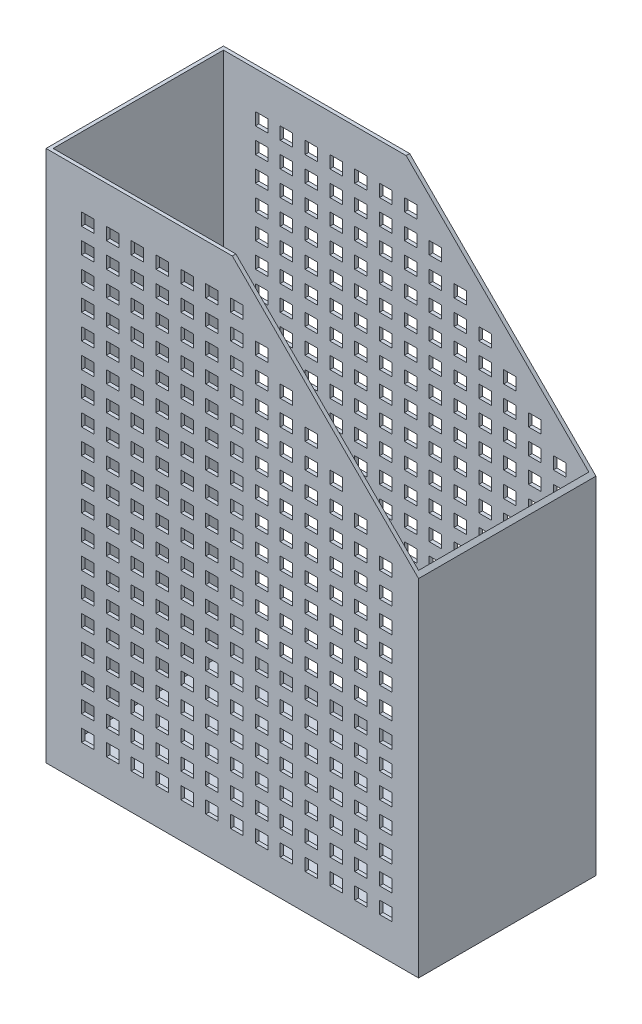
SolidWorks part; units mm, degrees
ref_plane "Front Plane" through (0, 0, 0) normal (0, 0, 1) x (1, 0, 0)
ref_plane "Top Plane" through (0, 0, 0) normal (0, 1, 0) x (1, 0, 0)
ref_plane "Right Plane" through (0, 0, 0) normal (1, 0, 0) x (0, 0, -1)
sketch "Sketch1" plane through (0, 0, 0) normal (0, 1, 0) x (1, 0, 0)
  line L1 (0, 0) -> (210, 0)
  line L2 (0, 0) -> (0, 100)
  line L3 (0, 100) -> (210, 100)
  line L4 (210, 0) -> (210, 100)
  dimension "D1" = 210
  dimension "D2" = 100
extrude "Boss-Extrude1" add sketch "Sketch1" along normal blind 300
sketch "Sketch2" plane through (0, 0, 0) normal (0, 0, 1) x (1, 0, 0)
  line L0 (210, 300) -> (105, 300)
  line L1 (0, 300) -> (210, 300) construction
  line L2 (105, 300) -> (210, 195)
  line L3 (210, 300) -> (210, 0) construction
  line L4 (210, 195) -> (210, 300)
  dimension "D1" = 45
extrude "Cut-Extrude1" cut sketch "Sketch2" against normal blind 300
shell "Shell1" thickness 2
sketch "Sketch3" plane through (0, 0, 0) normal (0, 0, 1) x (1, 0, 0)
  line L0 (0, 0) -> (210, 0) construction
  line L1 (20, 20) -> (27, 20)
  line L2 (20, 20) -> (20, 27)
  line L3 (20, 27) -> (27, 27)
  line L4 (27, 20) -> (27, 27)
  line L5 (0, 300) -> (0, 0) construction
  line L6 (34, 20) -> (34, 27)
  line L7 (34, 20) -> (41, 20)
  line L8 (41, 20) -> (41, 27)
  line L9 (34, 27) -> (41, 27)
  line L10 (48, 20) -> (48, 27)
  line L11 (48, 20) -> (55, 20)
  line L12 (55, 20) -> (55, 27)
  line L13 (48, 27) -> (55, 27)
  line L14 (62, 20) -> (62, 27)
  line L15 (62, 20) -> (69, 20)
  line L16 (69, 20) -> (69, 27)
  line L17 (62, 27) -> (69, 27)
  line L18 (76, 20) -> (76, 27)
  line L19 (76, 20) -> (83, 20)
  line L20 (83, 20) -> (83, 27)
  line L21 (76, 27) -> (83, 27)
  line L22 (90, 20) -> (90, 27)
  line L23 (90, 20) -> (97, 20)
  line L24 (97, 20) -> (97, 27)
  line L25 (90, 27) -> (97, 27)
  line L26 (104, 20) -> (104, 27)
  line L27 (104, 20) -> (111, 20)
  line L28 (111, 20) -> (111, 27)
  line L29 (104, 27) -> (111, 27)
  line L30 (118, 20) -> (118, 27)
  line L31 (118, 20) -> (125, 20)
  line L32 (125, 20) -> (125, 27)
  line L33 (118, 27) -> (125, 27)
  line L34 (132, 20) -> (132, 27)
  line L35 (132, 20) -> (139, 20)
  line L36 (139, 20) -> (139, 27)
  line L37 (132, 27) -> (139, 27)
  line L38 (146, 20) -> (146, 27)
  line L39 (146, 20) -> (153, 20)
  line L40 (153, 20) -> (153, 27)
  line L41 (146, 27) -> (153, 27)
  line L42 (160, 20) -> (160, 27)
  line L43 (160, 20) -> (167, 20)
  line L44 (167, 20) -> (167, 27)
  line L45 (160, 27) -> (167, 27)
  line L46 (174, 20) -> (174, 27)
  line L47 (174, 20) -> (181, 20)
  line L48 (181, 20) -> (181, 27)
  line L49 (174, 27) -> (181, 27)
  line L50 (188, 20) -> (188, 27)
  line L51 (188, 20) -> (195, 20)
  line L52 (195, 20) -> (195, 27)
  line L53 (188, 27) -> (195, 27)
  line L54 (34, 34) -> (34, 41)
  line L55 (34, 34) -> (41, 34)
  line L56 (41, 34) -> (41, 41)
  line L57 (34, 41) -> (41, 41)
  line L58 (48, 34) -> (48, 41)
  line L59 (48, 34) -> (55, 34)
  line L60 (55, 34) -> (55, 41)
  line L61 (48, 41) -> (55, 41)
  line L62 (62, 34) -> (62, 41)
  line L63 (62, 34) -> (69, 34)
  line L64 (69, 34) -> (69, 41)
  line L65 (62, 41) -> (69, 41)
  line L66 (76, 34) -> (76, 41)
  line L67 (76, 34) -> (83, 34)
  line L68 (83, 34) -> (83, 41)
  line L69 (76, 41) -> (83, 41)
  line L70 (90, 34) -> (90, 41)
  line L71 (90, 34) -> (97, 34)
  line L72 (97, 34) -> (97, 41)
  line L73 (90, 41) -> (97, 41)
  line L74 (104, 34) -> (104, 41)
  line L75 (104, 34) -> (111, 34)
  line L76 (111, 34) -> (111, 41)
  line L77 (104, 41) -> (111, 41)
  line L78 (118, 34) -> (118, 41)
  line L79 (118, 34) -> (125, 34)
  line L80 (125, 34) -> (125, 41)
  line L81 (118, 41) -> (125, 41)
  line L82 (132, 34) -> (132, 41)
  line L83 (132, 34) -> (139, 34)
  line L84 (139, 34) -> (139, 41)
  line L85 (132, 41) -> (139, 41)
  line L86 (146, 34) -> (146, 41)
  line L87 (146, 34) -> (153, 34)
  line L88 (153, 34) -> (153, 41)
  line L89 (146, 41) -> (153, 41)
  line L90 (160, 34) -> (160, 41)
  line L91 (160, 34) -> (167, 34)
  line L92 (167, 34) -> (167, 41)
  line L93 (160, 41) -> (167, 41)
  line L94 (174, 34) -> (174, 41)
  line L95 (174, 34) -> (181, 34)
  line L96 (181, 34) -> (181, 41)
  line L97 (174, 41) -> (181, 41)
  line L98 (188, 34) -> (188, 41)
  line L99 (188, 34) -> (195, 34)
  line L100 (195, 34) -> (195, 41)
  line L101 (188, 41) -> (195, 41)
  line L102 (34, 48) -> (34, 55)
  line L103 (34, 48) -> (41, 48)
  line L104 (41, 48) -> (41, 55)
  line L105 (34, 55) -> (41, 55)
  line L106 (48, 48) -> (48, 55)
  line L107 (48, 48) -> (55, 48)
  line L108 (55, 48) -> (55, 55)
  line L109 (48, 55) -> (55, 55)
  line L110 (62, 48) -> (62, 55)
  line L111 (62, 48) -> (69, 48)
  line L112 (69, 48) -> (69, 55)
  line L113 (62, 55) -> (69, 55)
  line L114 (76, 48) -> (76, 55)
  line L115 (76, 48) -> (83, 48)
  line L116 (83, 48) -> (83, 55)
  line L117 (76, 55) -> (83, 55)
  line L118 (90, 48) -> (90, 55)
  line L119 (90, 48) -> (97, 48)
  line L120 (97, 48) -> (97, 55)
  line L121 (90, 55) -> (97, 55)
  line L122 (104, 48) -> (104, 55)
  line L123 (104, 48) -> (111, 48)
  line L124 (111, 48) -> (111, 55)
  line L125 (104, 55) -> (111, 55)
  line L126 (118, 48) -> (118, 55)
  line L127 (118, 48) -> (125, 48)
  line L128 (125, 48) -> (125, 55)
  line L129 (118, 55) -> (125, 55)
  line L130 (132, 48) -> (132, 55)
  line L131 (132, 48) -> (139, 48)
  line L132 (139, 48) -> (139, 55)
  line L133 (132, 55) -> (139, 55)
  line L134 (146, 48) -> (146, 55)
  line L135 (146, 48) -> (153, 48)
  line L136 (153, 48) -> (153, 55)
  line L137 (146, 55) -> (153, 55)
  line L138 (160, 48) -> (160, 55)
  line L139 (160, 48) -> (167, 48)
  line L140 (167, 48) -> (167, 55)
  line L141 (160, 55) -> (167, 55)
  line L142 (174, 48) -> (174, 55)
  line L143 (174, 48) -> (181, 48)
  line L144 (181, 48) -> (181, 55)
  line L145 (174, 55) -> (181, 55)
  line L146 (188, 48) -> (188, 55)
  line L147 (188, 48) -> (195, 48)
  line L148 (195, 48) -> (195, 55)
  line L149 (188, 55) -> (195, 55)
  line L150 (34, 62) -> (34, 69)
  line L151 (34, 62) -> (41, 62)
  line L152 (41, 62) -> (41, 69)
  line L153 (34, 69) -> (41, 69)
  line L154 (48, 62) -> (48, 69)
  line L155 (48, 62) -> (55, 62)
  line L156 (55, 62) -> (55, 69)
  line L157 (48, 69) -> (55, 69)
  line L158 (62, 62) -> (62, 69)
  line L159 (62, 62) -> (69, 62)
  line L160 (69, 62) -> (69, 69)
  line L161 (62, 69) -> (69, 69)
  line L162 (76, 62) -> (76, 69)
  line L163 (76, 62) -> (83, 62)
  line L164 (83, 62) -> (83, 69)
  line L165 (76, 69) -> (83, 69)
  line L166 (90, 62) -> (90, 69)
  line L167 (90, 62) -> (97, 62)
  line L168 (97, 62) -> (97, 69)
  line L169 (90, 69) -> (97, 69)
  line L170 (104, 62) -> (104, 69)
  line L171 (104, 62) -> (111, 62)
  line L172 (111, 62) -> (111, 69)
  line L173 (104, 69) -> (111, 69)
  line L174 (118, 62) -> (118, 69)
  line L175 (118, 62) -> (125, 62)
  line L176 (125, 62) -> (125, 69)
  line L177 (118, 69) -> (125, 69)
  line L178 (132, 62) -> (132, 69)
  line L179 (132, 62) -> (139, 62)
  line L180 (139, 62) -> (139, 69)
  line L181 (132, 69) -> (139, 69)
  line L182 (146, 62) -> (146, 69)
  line L183 (146, 62) -> (153, 62)
  line L184 (153, 62) -> (153, 69)
  line L185 (146, 69) -> (153, 69)
  line L186 (160, 62) -> (160, 69)
  line L187 (160, 62) -> (167, 62)
  line L188 (167, 62) -> (167, 69)
  line L189 (160, 69) -> (167, 69)
  line L190 (174, 62) -> (174, 69)
  line L191 (174, 62) -> (181, 62)
  line L192 (181, 62) -> (181, 69)
  line L193 (174, 69) -> (181, 69)
  line L194 (188, 62) -> (188, 69)
  line L195 (188, 62) -> (195, 62)
  line L196 (195, 62) -> (195, 69)
  line L197 (188, 69) -> (195, 69)
  line L198 (34, 76) -> (34, 83)
  line L199 (34, 76) -> (41, 76)
  line L200 (41, 76) -> (41, 83)
  line L201 (34, 83) -> (41, 83)
  line L202 (48, 76) -> (48, 83)
  line L203 (48, 76) -> (55, 76)
  line L204 (55, 76) -> (55, 83)
  line L205 (48, 83) -> (55, 83)
  line L206 (62, 76) -> (62, 83)
  line L207 (62, 76) -> (69, 76)
  line L208 (69, 76) -> (69, 83)
  line L209 (62, 83) -> (69, 83)
  line L210 (76, 76) -> (76, 83)
  line L211 (76, 76) -> (83, 76)
  line L212 (83, 76) -> (83, 83)
  line L213 (76, 83) -> (83, 83)
  line L214 (90, 76) -> (90, 83)
  line L215 (90, 76) -> (97, 76)
  line L216 (97, 76) -> (97, 83)
  line L217 (90, 83) -> (97, 83)
  line L218 (104, 76) -> (104, 83)
  line L219 (104, 76) -> (111, 76)
  line L220 (111, 76) -> (111, 83)
  line L221 (104, 83) -> (111, 83)
  line L222 (118, 76) -> (118, 83)
  line L223 (118, 76) -> (125, 76)
  line L224 (125, 76) -> (125, 83)
  line L225 (118, 83) -> (125, 83)
  line L226 (132, 76) -> (132, 83)
  line L227 (132, 76) -> (139, 76)
  line L228 (139, 76) -> (139, 83)
  line L229 (132, 83) -> (139, 83)
  line L230 (146, 76) -> (146, 83)
  line L231 (146, 76) -> (153, 76)
  line L232 (153, 76) -> (153, 83)
  line L233 (146, 83) -> (153, 83)
  line L234 (160, 76) -> (160, 83)
  line L235 (160, 76) -> (167, 76)
  line L236 (167, 76) -> (167, 83)
  line L237 (160, 83) -> (167, 83)
  line L238 (174, 76) -> (174, 83)
  line L239 (174, 76) -> (181, 76)
  line L240 (181, 76) -> (181, 83)
  line L241 (174, 83) -> (181, 83)
  line L242 (188, 76) -> (188, 83)
  line L243 (188, 76) -> (195, 76)
  line L244 (195, 76) -> (195, 83)
  line L245 (188, 83) -> (195, 83)
  line L246 (34, 90) -> (34, 97)
  line L247 (34, 90) -> (41, 90)
  line L248 (41, 90) -> (41, 97)
  line L249 (34, 97) -> (41, 97)
  line L250 (48, 90) -> (48, 97)
  line L251 (48, 90) -> (55, 90)
  line L252 (55, 90) -> (55, 97)
  line L253 (48, 97) -> (55, 97)
  line L254 (62, 90) -> (62, 97)
  line L255 (62, 90) -> (69, 90)
  line L256 (69, 90) -> (69, 97)
  line L257 (62, 97) -> (69, 97)
  line L258 (76, 90) -> (76, 97)
  line L259 (76, 90) -> (83, 90)
  line L260 (83, 90) -> (83, 97)
  line L261 (76, 97) -> (83, 97)
  line L262 (90, 90) -> (90, 97)
  line L263 (90, 90) -> (97, 90)
  line L264 (97, 90) -> (97, 97)
  line L265 (90, 97) -> (97, 97)
  line L266 (104, 90) -> (104, 97)
  line L267 (104, 90) -> (111, 90)
  line L268 (111, 90) -> (111, 97)
  line L269 (104, 97) -> (111, 97)
  line L270 (118, 90) -> (118, 97)
  line L271 (118, 90) -> (125, 90)
  line L272 (125, 90) -> (125, 97)
  line L273 (118, 97) -> (125, 97)
  line L274 (132, 90) -> (132, 97)
  line L275 (132, 90) -> (139, 90)
  line L276 (139, 90) -> (139, 97)
  line L277 (132, 97) -> (139, 97)
  line L278 (146, 90) -> (146, 97)
  line L279 (146, 90) -> (153, 90)
  line L280 (153, 90) -> (153, 97)
  line L281 (146, 97) -> (153, 97)
  line L282 (160, 90) -> (160, 97)
  line L283 (160, 90) -> (167, 90)
  line L284 (167, 90) -> (167, 97)
  line L285 (160, 97) -> (167, 97)
  line L286 (174, 90) -> (174, 97)
  line L287 (174, 90) -> (181, 90)
  line L288 (181, 90) -> (181, 97)
  line L289 (174, 97) -> (181, 97)
  line L290 (188, 90) -> (188, 97)
  line L291 (188, 90) -> (195, 90)
  line L292 (195, 90) -> (195, 97)
  line L293 (188, 97) -> (195, 97)
  line L294 (34, 104) -> (34, 111)
  line L295 (34, 104) -> (41, 104)
  line L296 (41, 104) -> (41, 111)
  line L297 (34, 111) -> (41, 111)
  line L298 (48, 104) -> (48, 111)
  line L299 (48, 104) -> (55, 104)
  line L300 (55, 104) -> (55, 111)
  line L301 (48, 111) -> (55, 111)
  line L302 (62, 104) -> (62, 111)
  line L303 (62, 104) -> (69, 104)
  line L304 (69, 104) -> (69, 111)
  line L305 (62, 111) -> (69, 111)
  line L306 (76, 104) -> (76, 111)
  line L307 (76, 104) -> (83, 104)
  line L308 (83, 104) -> (83, 111)
  line L309 (76, 111) -> (83, 111)
  line L310 (90, 104) -> (90, 111)
  line L311 (90, 104) -> (97, 104)
  line L312 (97, 104) -> (97, 111)
  line L313 (90, 111) -> (97, 111)
  line L314 (104, 104) -> (104, 111)
  line L315 (104, 104) -> (111, 104)
  line L316 (111, 104) -> (111, 111)
  line L317 (104, 111) -> (111, 111)
  line L318 (118, 104) -> (118, 111)
  line L319 (118, 104) -> (125, 104)
  line L320 (125, 104) -> (125, 111)
  line L321 (118, 111) -> (125, 111)
  line L322 (132, 104) -> (132, 111)
  line L323 (132, 104) -> (139, 104)
  line L324 (139, 104) -> (139, 111)
  line L325 (132, 111) -> (139, 111)
  line L326 (146, 104) -> (146, 111)
  line L327 (146, 104) -> (153, 104)
  line L328 (153, 104) -> (153, 111)
  line L329 (146, 111) -> (153, 111)
  line L330 (160, 104) -> (160, 111)
  line L331 (160, 104) -> (167, 104)
  line L332 (167, 104) -> (167, 111)
  line L333 (160, 111) -> (167, 111)
  line L334 (174, 104) -> (174, 111)
  line L335 (174, 104) -> (181, 104)
  line L336 (181, 104) -> (181, 111)
  line L337 (174, 111) -> (181, 111)
  line L338 (188, 104) -> (188, 111)
  line L339 (188, 104) -> (195, 104)
  line L340 (195, 104) -> (195, 111)
  line L341 (188, 111) -> (195, 111)
  line L342 (34, 118) -> (34, 125)
  line L343 (34, 118) -> (41, 118)
  line L344 (41, 118) -> (41, 125)
  line L345 (34, 125) -> (41, 125)
  line L346 (48, 118) -> (48, 125)
  line L347 (48, 118) -> (55, 118)
  line L348 (55, 118) -> (55, 125)
  line L349 (48, 125) -> (55, 125)
  line L350 (62, 118) -> (62, 125)
  line L351 (62, 118) -> (69, 118)
  line L352 (69, 118) -> (69, 125)
  line L353 (62, 125) -> (69, 125)
  line L354 (76, 118) -> (76, 125)
  line L355 (76, 118) -> (83, 118)
  line L356 (83, 118) -> (83, 125)
  line L357 (76, 125) -> (83, 125)
  line L358 (90, 118) -> (90, 125)
  line L359 (90, 118) -> (97, 118)
  line L360 (97, 118) -> (97, 125)
  line L361 (90, 125) -> (97, 125)
  line L362 (104, 118) -> (104, 125)
  line L363 (104, 118) -> (111, 118)
  line L364 (111, 118) -> (111, 125)
  line L365 (104, 125) -> (111, 125)
  line L366 (118, 118) -> (118, 125)
  line L367 (118, 118) -> (125, 118)
  line L368 (125, 118) -> (125, 125)
  line L369 (118, 125) -> (125, 125)
  line L370 (132, 118) -> (132, 125)
  line L371 (132, 118) -> (139, 118)
  line L372 (139, 118) -> (139, 125)
  line L373 (132, 125) -> (139, 125)
  line L374 (146, 118) -> (146, 125)
  line L375 (146, 118) -> (153, 118)
  line L376 (153, 118) -> (153, 125)
  line L377 (146, 125) -> (153, 125)
  line L378 (160, 118) -> (160, 125)
  line L379 (160, 118) -> (167, 118)
  line L380 (167, 118) -> (167, 125)
  line L381 (160, 125) -> (167, 125)
  line L382 (174, 118) -> (174, 125)
  line L383 (174, 118) -> (181, 118)
  line L384 (181, 118) -> (181, 125)
  line L385 (174, 125) -> (181, 125)
  line L386 (188, 118) -> (188, 125)
  line L387 (188, 118) -> (195, 118)
  line L388 (195, 118) -> (195, 125)
  line L389 (188, 125) -> (195, 125)
  line L390 (34, 132) -> (34, 139)
  line L391 (34, 132) -> (41, 132)
  line L392 (41, 132) -> (41, 139)
  line L393 (34, 139) -> (41, 139)
  line L394 (48, 132) -> (48, 139)
  line L395 (48, 132) -> (55, 132)
  line L396 (55, 132) -> (55, 139)
  line L397 (48, 139) -> (55, 139)
  line L398 (62, 132) -> (62, 139)
  line L399 (62, 132) -> (69, 132)
  line L400 (69, 132) -> (69, 139)
  line L401 (62, 139) -> (69, 139)
  line L402 (76, 132) -> (76, 139)
  line L403 (76, 132) -> (83, 132)
  line L404 (83, 132) -> (83, 139)
  line L405 (76, 139) -> (83, 139)
  line L406 (90, 132) -> (90, 139)
  line L407 (90, 132) -> (97, 132)
  line L408 (97, 132) -> (97, 139)
  line L409 (90, 139) -> (97, 139)
  line L410 (104, 132) -> (104, 139)
  line L411 (104, 132) -> (111, 132)
  line L412 (111, 132) -> (111, 139)
  line L413 (104, 139) -> (111, 139)
  line L414 (118, 132) -> (118, 139)
  line L415 (118, 132) -> (125, 132)
  line L416 (125, 132) -> (125, 139)
  line L417 (118, 139) -> (125, 139)
  line L418 (132, 132) -> (132, 139)
  line L419 (132, 132) -> (139, 132)
  line L420 (139, 132) -> (139, 139)
  line L421 (132, 139) -> (139, 139)
  line L422 (146, 132) -> (146, 139)
  line L423 (146, 132) -> (153, 132)
  line L424 (153, 132) -> (153, 139)
  line L425 (146, 139) -> (153, 139)
  line L426 (160, 132) -> (160, 139)
  line L427 (160, 132) -> (167, 132)
  line L428 (167, 132) -> (167, 139)
  line L429 (160, 139) -> (167, 139)
  line L430 (174, 132) -> (174, 139)
  line L431 (174, 132) -> (181, 132)
  line L432 (181, 132) -> (181, 139)
  line L433 (174, 139) -> (181, 139)
  line L434 (188, 132) -> (188, 139)
  line L435 (188, 132) -> (195, 132)
  line L436 (195, 132) -> (195, 139)
  line L437 (188, 139) -> (195, 139)
  line L438 (34, 146) -> (34, 153)
  line L439 (34, 146) -> (41, 146)
  line L440 (41, 146) -> (41, 153)
  line L441 (34, 153) -> (41, 153)
  line L442 (48, 146) -> (48, 153)
  line L443 (48, 146) -> (55, 146)
  line L444 (55, 146) -> (55, 153)
  line L445 (48, 153) -> (55, 153)
  line L446 (62, 146) -> (62, 153)
  line L447 (62, 146) -> (69, 146)
  line L448 (69, 146) -> (69, 153)
  line L449 (62, 153) -> (69, 153)
  line L450 (76, 146) -> (76, 153)
  line L451 (76, 146) -> (83, 146)
  line L452 (83, 146) -> (83, 153)
  line L453 (76, 153) -> (83, 153)
  line L454 (90, 146) -> (90, 153)
  line L455 (90, 146) -> (97, 146)
  line L456 (97, 146) -> (97, 153)
  line L457 (90, 153) -> (97, 153)
  line L458 (104, 146) -> (104, 153)
  line L459 (104, 146) -> (111, 146)
  line L460 (111, 146) -> (111, 153)
  line L461 (104, 153) -> (111, 153)
  line L462 (118, 146) -> (118, 153)
  line L463 (118, 146) -> (125, 146)
  line L464 (125, 146) -> (125, 153)
  line L465 (118, 153) -> (125, 153)
  line L466 (132, 146) -> (132, 153)
  line L467 (132, 146) -> (139, 146)
  line L468 (139, 146) -> (139, 153)
  line L469 (132, 153) -> (139, 153)
  line L470 (146, 146) -> (146, 153)
  line L471 (146, 146) -> (153, 146)
  line L472 (153, 146) -> (153, 153)
  line L473 (146, 153) -> (153, 153)
  line L474 (160, 146) -> (160, 153)
  line L475 (160, 146) -> (167, 146)
  line L476 (167, 146) -> (167, 153)
  line L477 (160, 153) -> (167, 153)
  line L478 (174, 146) -> (174, 153)
  line L479 (174, 146) -> (181, 146)
  line L480 (181, 146) -> (181, 153)
  line L481 (174, 153) -> (181, 153)
  line L482 (188, 146) -> (188, 153)
  line L483 (188, 146) -> (195, 146)
  line L484 (195, 146) -> (195, 153)
  line L485 (188, 153) -> (195, 153)
  line L486 (34, 160) -> (34, 167)
  line L487 (34, 160) -> (41, 160)
  line L488 (41, 160) -> (41, 167)
  line L489 (34, 167) -> (41, 167)
  line L490 (48, 160) -> (48, 167)
  line L491 (48, 160) -> (55, 160)
  line L492 (55, 160) -> (55, 167)
  line L493 (48, 167) -> (55, 167)
  line L494 (62, 160) -> (62, 167)
  line L495 (62, 160) -> (69, 160)
  line L496 (69, 160) -> (69, 167)
  line L497 (62, 167) -> (69, 167)
  line L498 (76, 160) -> (76, 167)
  line L499 (76, 160) -> (83, 160)
  line L500 (83, 160) -> (83, 167)
  line L501 (76, 167) -> (83, 167)
  line L502 (90, 160) -> (90, 167)
  line L503 (90, 160) -> (97, 160)
  line L504 (97, 160) -> (97, 167)
  line L505 (90, 167) -> (97, 167)
  line L506 (104, 160) -> (104, 167)
  line L507 (104, 160) -> (111, 160)
  line L508 (111, 160) -> (111, 167)
  line L509 (104, 167) -> (111, 167)
  line L510 (118, 160) -> (118, 167)
  line L511 (118, 160) -> (125, 160)
  line L512 (125, 160) -> (125, 167)
  line L513 (118, 167) -> (125, 167)
  line L514 (132, 160) -> (132, 167)
  line L515 (132, 160) -> (139, 160)
  line L516 (139, 160) -> (139, 167)
  line L517 (132, 167) -> (139, 167)
  line L518 (146, 160) -> (146, 167)
  line L519 (146, 160) -> (153, 160)
  line L520 (153, 160) -> (153, 167)
  line L521 (146, 167) -> (153, 167)
  line L522 (160, 160) -> (160, 167)
  line L523 (160, 160) -> (167, 160)
  line L524 (167, 160) -> (167, 167)
  line L525 (160, 167) -> (167, 167)
  line L526 (174, 160) -> (174, 167)
  line L527 (174, 160) -> (181, 160)
  line L528 (181, 160) -> (181, 167)
  line L529 (174, 167) -> (181, 167)
  line L530 (188, 160) -> (188, 167)
  line L531 (188, 160) -> (195, 160)
  line L532 (195, 160) -> (195, 167)
  line L533 (188, 167) -> (195, 167)
  line L534 (34, 174) -> (34, 181)
  line L535 (34, 174) -> (41, 174)
  line L536 (41, 174) -> (41, 181)
  line L537 (34, 181) -> (41, 181)
  line L538 (48, 174) -> (48, 181)
  line L539 (48, 174) -> (55, 174)
  line L540 (55, 174) -> (55, 181)
  line L541 (48, 181) -> (55, 181)
  line L542 (62, 174) -> (62, 181)
  line L543 (62, 174) -> (69, 174)
  line L544 (69, 174) -> (69, 181)
  line L545 (62, 181) -> (69, 181)
  line L546 (76, 174) -> (76, 181)
  line L547 (76, 174) -> (83, 174)
  line L548 (83, 174) -> (83, 181)
  line L549 (76, 181) -> (83, 181)
  line L550 (90, 174) -> (90, 181)
  line L551 (90, 174) -> (97, 174)
  line L552 (97, 174) -> (97, 181)
  line L553 (90, 181) -> (97, 181)
  line L554 (104, 174) -> (104, 181)
  line L555 (104, 174) -> (111, 174)
  line L556 (111, 174) -> (111, 181)
  line L557 (104, 181) -> (111, 181)
  line L558 (118, 174) -> (118, 181)
  line L559 (118, 174) -> (125, 174)
  line L560 (125, 174) -> (125, 181)
  line L561 (118, 181) -> (125, 181)
  line L562 (132, 174) -> (132, 181)
  line L563 (132, 174) -> (139, 174)
  line L564 (139, 174) -> (139, 181)
  line L565 (132, 181) -> (139, 181)
  line L566 (146, 174) -> (146, 181)
  line L567 (146, 174) -> (153, 174)
  line L568 (153, 174) -> (153, 181)
  line L569 (146, 181) -> (153, 181)
  line L570 (160, 174) -> (160, 181)
  line L571 (160, 174) -> (167, 174)
  line L572 (167, 174) -> (167, 181)
  line L573 (160, 181) -> (167, 181)
  line L574 (174, 174) -> (174, 181)
  line L575 (174, 174) -> (181, 174)
  line L576 (181, 174) -> (181, 181)
  line L577 (174, 181) -> (181, 181)
  line L578 (188, 174) -> (188, 181)
  line L579 (188, 174) -> (195, 174)
  line L580 (195, 174) -> (195, 181)
  line L581 (188, 181) -> (195, 181)
  line L582 (34, 188) -> (34, 195)
  line L583 (34, 188) -> (41, 188)
  line L584 (41, 188) -> (41, 195)
  line L585 (34, 195) -> (41, 195)
  line L586 (48, 188) -> (48, 195)
  line L587 (48, 188) -> (55, 188)
  line L588 (55, 188) -> (55, 195)
  line L589 (48, 195) -> (55, 195)
  line L590 (62, 188) -> (62, 195)
  line L591 (62, 188) -> (69, 188)
  line L592 (69, 188) -> (69, 195)
  line L593 (62, 195) -> (69, 195)
  line L594 (76, 188) -> (76, 195)
  line L595 (76, 188) -> (83, 188)
  line L596 (83, 188) -> (83, 195)
  line L597 (76, 195) -> (83, 195)
  line L598 (90, 188) -> (90, 195)
  line L599 (90, 188) -> (97, 188)
  line L600 (97, 188) -> (97, 195)
  line L601 (90, 195) -> (97, 195)
  line L602 (104, 188) -> (104, 195)
  line L603 (104, 188) -> (111, 188)
  line L604 (111, 188) -> (111, 195)
  line L605 (104, 195) -> (111, 195)
  line L606 (118, 188) -> (118, 195)
  line L607 (118, 188) -> (125, 188)
  line L608 (125, 188) -> (125, 195)
  line L609 (118, 195) -> (125, 195)
  line L610 (132, 188) -> (132, 195)
  line L611 (132, 188) -> (139, 188)
  line L612 (139, 188) -> (139, 195)
  line L613 (132, 195) -> (139, 195)
  line L614 (146, 188) -> (146, 195)
  line L615 (146, 188) -> (153, 188)
  line L616 (153, 188) -> (153, 195)
  line L617 (146, 195) -> (153, 195)
  line L618 (160, 188) -> (160, 195)
  line L619 (160, 188) -> (167, 188)
  line L620 (167, 188) -> (167, 195)
  line L621 (160, 195) -> (167, 195)
  line L622 (174, 188) -> (174, 195)
  line L623 (174, 188) -> (181, 188)
  line L624 (181, 188) -> (181, 195)
  line L625 (174, 195) -> (181, 195)
  line L626 (188, 188) -> (188, 195)
  line L627 (188, 188) -> (195, 188)
  line L628 (195, 188) -> (195, 195)
  line L629 (188, 195) -> (195, 195)
  line L630 (34, 202) -> (34, 209)
  line L631 (34, 202) -> (41, 202)
  line L632 (41, 202) -> (41, 209)
  line L633 (34, 209) -> (41, 209)
  line L634 (48, 202) -> (48, 209)
  line L635 (48, 202) -> (55, 202)
  line L636 (55, 202) -> (55, 209)
  line L637 (48, 209) -> (55, 209)
  line L638 (62, 202) -> (62, 209)
  line L639 (62, 202) -> (69, 202)
  line L640 (69, 202) -> (69, 209)
  line L641 (62, 209) -> (69, 209)
  line L642 (76, 202) -> (76, 209)
  line L643 (76, 202) -> (83, 202)
  line L644 (83, 202) -> (83, 209)
  line L645 (76, 209) -> (83, 209)
  line L646 (90, 202) -> (90, 209)
  line L647 (90, 202) -> (97, 202)
  line L648 (97, 202) -> (97, 209)
  line L649 (90, 209) -> (97, 209)
  line L650 (104, 202) -> (104, 209)
  line L651 (104, 202) -> (111, 202)
  line L652 (111, 202) -> (111, 209)
  line L653 (104, 209) -> (111, 209)
  line L654 (118, 202) -> (118, 209)
  line L655 (118, 202) -> (125, 202)
  line L656 (125, 202) -> (125, 209)
  line L657 (118, 209) -> (125, 209)
  line L658 (132, 202) -> (132, 209)
  line L659 (132, 202) -> (139, 202)
  line L660 (139, 202) -> (139, 209)
  line L661 (132, 209) -> (139, 209)
  line L662 (146, 202) -> (146, 209)
  line L663 (146, 202) -> (153, 202)
  line L664 (153, 202) -> (153, 209)
  line L665 (146, 209) -> (153, 209)
  line L666 (160, 202) -> (160, 209)
  line L667 (160, 202) -> (167, 202)
  line L668 (167, 202) -> (167, 209)
  line L669 (160, 209) -> (167, 209)
  line L670 (174, 202) -> (174, 209)
  line L671 (174, 202) -> (181, 202)
  line L672 (181, 202) -> (181, 209)
  line L673 (174, 209) -> (181, 209)
  line L674 (188, 202) -> (188, 209) [skipped]
  line L675 (188, 202) -> (195, 202) [skipped]
  line L676 (195, 202) -> (195, 209) [skipped]
  line L677 (188, 209) -> (195, 209) [skipped]
  line L678 (34, 216) -> (34, 223)
  line L679 (34, 216) -> (41, 216)
  line L680 (41, 216) -> (41, 223)
  line L681 (34, 223) -> (41, 223)
  line L682 (48, 216) -> (48, 223)
  line L683 (48, 216) -> (55, 216)
  line L684 (55, 216) -> (55, 223)
  line L685 (48, 223) -> (55, 223)
  line L686 (62, 216) -> (62, 223)
  line L687 (62, 216) -> (69, 216)
  line L688 (69, 216) -> (69, 223)
  line L689 (62, 223) -> (69, 223)
  line L690 (76, 216) -> (76, 223)
  line L691 (76, 216) -> (83, 216)
  line L692 (83, 216) -> (83, 223)
  line L693 (76, 223) -> (83, 223)
  line L694 (90, 216) -> (90, 223)
  line L695 (90, 216) -> (97, 216)
  line L696 (97, 216) -> (97, 223)
  line L697 (90, 223) -> (97, 223)
  line L698 (104, 216) -> (104, 223)
  line L699 (104, 216) -> (111, 216)
  line L700 (111, 216) -> (111, 223)
  line L701 (104, 223) -> (111, 223)
  line L702 (118, 216) -> (118, 223)
  line L703 (118, 216) -> (125, 216)
  line L704 (125, 216) -> (125, 223)
  line L705 (118, 223) -> (125, 223)
  line L706 (132, 216) -> (132, 223)
  line L707 (132, 216) -> (139, 216)
  line L708 (139, 216) -> (139, 223)
  line L709 (132, 223) -> (139, 223)
  line L710 (146, 216) -> (146, 223)
  line L711 (146, 216) -> (153, 216)
  line L712 (153, 216) -> (153, 223)
  line L713 (146, 223) -> (153, 223)
  line L714 (160, 216) -> (160, 223)
  line L715 (160, 216) -> (167, 216)
  line L716 (167, 216) -> (167, 223)
  line L717 (160, 223) -> (167, 223)
  line L718 (174, 216) -> (174, 223) [skipped]
  line L719 (174, 216) -> (181, 216) [skipped]
  line L720 (181, 216) -> (181, 223) [skipped]
  line L721 (174, 223) -> (181, 223) [skipped]
  line L722 (188, 216) -> (188, 223) [skipped]
  line L723 (188, 216) -> (195, 216) [skipped]
  line L724 (195, 216) -> (195, 223) [skipped]
  line L725 (188, 223) -> (195, 223) [skipped]
  line L726 (34, 230) -> (34, 237)
  line L727 (34, 230) -> (41, 230)
  line L728 (41, 230) -> (41, 237)
  line L729 (34, 237) -> (41, 237)
  line L730 (48, 230) -> (48, 237)
  line L731 (48, 230) -> (55, 230)
  line L732 (55, 230) -> (55, 237)
  line L733 (48, 237) -> (55, 237)
  line L734 (62, 230) -> (62, 237)
  line L735 (62, 230) -> (69, 230)
  line L736 (69, 230) -> (69, 237)
  line L737 (62, 237) -> (69, 237)
  line L738 (76, 230) -> (76, 237)
  line L739 (76, 230) -> (83, 230)
  line L740 (83, 230) -> (83, 237)
  line L741 (76, 237) -> (83, 237)
  line L742 (90, 230) -> (90, 237)
  line L743 (90, 230) -> (97, 230)
  line L744 (97, 230) -> (97, 237)
  line L745 (90, 237) -> (97, 237)
  line L746 (104, 230) -> (104, 237)
  line L747 (104, 230) -> (111, 230)
  line L748 (111, 230) -> (111, 237)
  line L749 (104, 237) -> (111, 237)
  line L750 (118, 230) -> (118, 237)
  line L751 (118, 230) -> (125, 230)
  line L752 (125, 230) -> (125, 237)
  line L753 (118, 237) -> (125, 237)
  line L754 (132, 230) -> (132, 237)
  line L755 (132, 230) -> (139, 230)
  line L756 (139, 230) -> (139, 237)
  line L757 (132, 237) -> (139, 237)
  line L758 (146, 230) -> (146, 237)
  line L759 (146, 230) -> (153, 230)
  line L760 (153, 230) -> (153, 237)
  line L761 (146, 237) -> (153, 237)
  line L762 (160, 230) -> (160, 237) [skipped]
  line L763 (160, 230) -> (167, 230) [skipped]
  line L764 (167, 230) -> (167, 237) [skipped]
  line L765 (160, 237) -> (167, 237) [skipped]
  line L766 (174, 230) -> (174, 237) [skipped]
  line L767 (174, 230) -> (181, 230) [skipped]
  line L768 (181, 230) -> (181, 237) [skipped]
  line L769 (174, 237) -> (181, 237) [skipped]
  line L770 (188, 230) -> (188, 237)
  line L771 (188, 230) -> (195, 230)
  line L772 (195, 230) -> (195, 237)
  line L773 (188, 237) -> (195, 237)
  line L774 (34, 244) -> (34, 251)
  line L775 (34, 244) -> (41, 244)
  line L776 (41, 244) -> (41, 251)
  line L777 (34, 251) -> (41, 251)
  line L778 (48, 244) -> (48, 251)
  line L779 (48, 244) -> (55, 244)
  line L780 (55, 244) -> (55, 251)
  line L781 (48, 251) -> (55, 251)
  line L782 (62, 244) -> (62, 251)
  line L783 (62, 244) -> (69, 244)
  line L784 (69, 244) -> (69, 251)
  line L785 (62, 251) -> (69, 251)
  line L786 (76, 244) -> (76, 251)
  line L787 (76, 244) -> (83, 244)
  line L788 (83, 244) -> (83, 251)
  line L789 (76, 251) -> (83, 251)
  line L790 (90, 244) -> (90, 251)
  line L791 (90, 244) -> (97, 244)
  line L792 (97, 244) -> (97, 251)
  line L793 (90, 251) -> (97, 251)
  line L794 (104, 244) -> (104, 251)
  line L795 (104, 244) -> (111, 244)
  line L796 (111, 244) -> (111, 251)
  line L797 (104, 251) -> (111, 251)
  line L798 (118, 244) -> (118, 251)
  line L799 (118, 244) -> (125, 244)
  line L800 (125, 244) -> (125, 251)
  line L801 (118, 251) -> (125, 251)
  line L802 (132, 244) -> (132, 251)
  line L803 (132, 244) -> (139, 244)
  line L804 (139, 244) -> (139, 251)
  line L805 (132, 251) -> (139, 251)
  line L806 (146, 244) -> (146, 251) [skipped]
  line L807 (146, 244) -> (153, 244) [skipped]
  line L808 (153, 244) -> (153, 251) [skipped]
  line L809 (146, 251) -> (153, 251) [skipped]
  line L810 (160, 244) -> (160, 251) [skipped]
  line L811 (160, 244) -> (167, 244) [skipped]
  line L812 (167, 244) -> (167, 251) [skipped]
  line L813 (160, 251) -> (167, 251) [skipped]
  line L814 (174, 244) -> (174, 251)
  line L815 (174, 244) -> (181, 244)
  line L816 (181, 244) -> (181, 251)
  line L817 (174, 251) -> (181, 251)
  line L818 (188, 244) -> (188, 251)
  line L819 (188, 244) -> (195, 244)
  line L820 (195, 244) -> (195, 251)
  line L821 (188, 251) -> (195, 251)
  line L822 (34, 258) -> (34, 265)
  line L823 (34, 258) -> (41, 258)
  line L824 (41, 258) -> (41, 265)
  line L825 (34, 265) -> (41, 265)
  line L826 (48, 258) -> (48, 265)
  line L827 (48, 258) -> (55, 258)
  line L828 (55, 258) -> (55, 265)
  line L829 (48, 265) -> (55, 265)
  line L830 (62, 258) -> (62, 265)
  line L831 (62, 258) -> (69, 258)
  line L832 (69, 258) -> (69, 265)
  line L833 (62, 265) -> (69, 265)
  line L834 (76, 258) -> (76, 265)
  line L835 (76, 258) -> (83, 258)
  line L836 (83, 258) -> (83, 265)
  line L837 (76, 265) -> (83, 265)
  line L838 (90, 258) -> (90, 265)
  line L839 (90, 258) -> (97, 258)
  line L840 (97, 258) -> (97, 265)
  line L841 (90, 265) -> (97, 265)
  line L842 (104, 258) -> (104, 265)
  line L843 (104, 258) -> (111, 258)
  line L844 (111, 258) -> (111, 265)
  line L845 (104, 265) -> (111, 265)
  line L846 (118, 258) -> (118, 265)
  line L847 (118, 258) -> (125, 258)
  line L848 (125, 258) -> (125, 265)
  line L849 (118, 265) -> (125, 265)
  line L850 (132, 258) -> (132, 265) [skipped]
  line L851 (132, 258) -> (139, 258) [skipped]
  line L852 (139, 258) -> (139, 265) [skipped]
  line L853 (132, 265) -> (139, 265) [skipped]
  line L854 (146, 258) -> (146, 265) [skipped]
  line L855 (146, 258) -> (153, 258) [skipped]
  line L856 (153, 258) -> (153, 265) [skipped]
  line L857 (146, 265) -> (153, 265) [skipped]
  line L858 (160, 258) -> (160, 265)
  line L859 (160, 258) -> (167, 258)
  line L860 (167, 258) -> (167, 265)
  line L861 (160, 265) -> (167, 265)
  line L862 (174, 258) -> (174, 265)
  line L863 (174, 258) -> (181, 258)
  line L864 (181, 258) -> (181, 265)
  line L865 (174, 265) -> (181, 265)
  line L866 (188, 258) -> (188, 265)
  line L867 (188, 258) -> (195, 258)
  line L868 (195, 258) -> (195, 265)
  line L869 (188, 265) -> (195, 265)
  line L870 (34, 272) -> (34, 279)
  line L871 (34, 272) -> (41, 272)
  line L872 (41, 272) -> (41, 279)
  line L873 (34, 279) -> (41, 279)
  line L874 (48, 272) -> (48, 279)
  line L875 (48, 272) -> (55, 272)
  line L876 (55, 272) -> (55, 279)
  line L877 (48, 279) -> (55, 279)
  line L878 (62, 272) -> (62, 279)
  line L879 (62, 272) -> (69, 272)
  line L880 (69, 272) -> (69, 279)
  line L881 (62, 279) -> (69, 279)
  line L882 (76, 272) -> (76, 279)
  line L883 (76, 272) -> (83, 272)
  line L884 (83, 272) -> (83, 279)
  line L885 (76, 279) -> (83, 279)
  line L886 (90, 272) -> (90, 279)
  line L887 (90, 272) -> (97, 272)
  line L888 (97, 272) -> (97, 279)
  line L889 (90, 279) -> (97, 279)
  line L890 (104, 272) -> (104, 279)
  line L891 (104, 272) -> (111, 272)
  line L892 (111, 272) -> (111, 279)
  line L893 (104, 279) -> (111, 279)
  line L894 (118, 272) -> (118, 279) [skipped]
  line L895 (118, 272) -> (125, 272) [skipped]
  line L896 (125, 272) -> (125, 279) [skipped]
  line L897 (118, 279) -> (125, 279) [skipped]
  line L898 (132, 272) -> (132, 279) [skipped]
  line L899 (132, 272) -> (139, 272) [skipped]
  line L900 (139, 272) -> (139, 279) [skipped]
  line L901 (132, 279) -> (139, 279) [skipped]
  line L902 (146, 272) -> (146, 279)
  line L903 (146, 272) -> (153, 272)
  line L904 (153, 272) -> (153, 279)
  line L905 (146, 279) -> (153, 279)
  line L906 (160, 272) -> (160, 279)
  line L907 (160, 272) -> (167, 272)
  line L908 (167, 272) -> (167, 279)
  line L909 (160, 279) -> (167, 279)
  line L910 (174, 272) -> (174, 279)
  line L911 (174, 272) -> (181, 272)
  line L912 (181, 272) -> (181, 279)
  line L913 (174, 279) -> (181, 279)
  line L914 (188, 272) -> (188, 279)
  line L915 (188, 272) -> (195, 272)
  line L916 (195, 272) -> (195, 279)
  line L917 (188, 279) -> (195, 279)
  line L918 (20, 34) -> (20, 41)
  line L919 (20, 34) -> (27, 34)
  line L920 (27, 34) -> (27, 41)
  line L921 (20, 41) -> (27, 41)
  line L922 (20, 48) -> (20, 55)
  line L923 (20, 48) -> (27, 48)
  line L924 (27, 48) -> (27, 55)
  line L925 (20, 55) -> (27, 55)
  line L926 (20, 62) -> (20, 69)
  line L927 (20, 62) -> (27, 62)
  line L928 (27, 62) -> (27, 69)
  line L929 (20, 69) -> (27, 69)
  line L930 (20, 76) -> (20, 83)
  line L931 (20, 76) -> (27, 76)
  line L932 (27, 76) -> (27, 83)
  line L933 (20, 83) -> (27, 83)
  line L934 (20, 90) -> (20, 97)
  line L935 (20, 90) -> (27, 90)
  line L936 (27, 90) -> (27, 97)
  line L937 (20, 97) -> (27, 97)
  line L938 (20, 104) -> (20, 111)
  line L939 (20, 104) -> (27, 104)
  line L940 (27, 104) -> (27, 111)
  line L941 (20, 111) -> (27, 111)
  line L942 (20, 118) -> (20, 125)
  line L943 (20, 118) -> (27, 118)
  line L944 (27, 118) -> (27, 125)
  line L945 (20, 125) -> (27, 125)
  line L946 (20, 132) -> (20, 139)
  line L947 (20, 132) -> (27, 132)
  line L948 (27, 132) -> (27, 139)
  line L949 (20, 139) -> (27, 139)
  line L950 (20, 146) -> (20, 153)
  line L951 (20, 146) -> (27, 146)
  line L952 (27, 146) -> (27, 153)
  line L953 (20, 153) -> (27, 153)
  line L954 (20, 160) -> (20, 167)
  line L955 (20, 160) -> (27, 160)
  line L956 (27, 160) -> (27, 167)
  line L957 (20, 167) -> (27, 167)
  line L958 (20, 174) -> (20, 181)
  line L959 (20, 174) -> (27, 174)
  line L960 (27, 174) -> (27, 181)
  line L961 (20, 181) -> (27, 181)
  line L962 (20, 188) -> (20, 195)
  line L963 (20, 188) -> (27, 188)
  line L964 (27, 188) -> (27, 195)
  line L965 (20, 195) -> (27, 195)
  line L966 (20, 202) -> (20, 209)
  line L967 (20, 202) -> (27, 202)
  line L968 (27, 202) -> (27, 209)
  line L969 (20, 209) -> (27, 209)
  line L970 (20, 216) -> (20, 223)
  line L971 (20, 216) -> (27, 216)
  line L972 (27, 216) -> (27, 223)
  line L973 (20, 223) -> (27, 223)
  line L974 (20, 230) -> (20, 237)
  line L975 (20, 230) -> (27, 230)
  line L976 (27, 230) -> (27, 237)
  line L977 (20, 237) -> (27, 237)
  line L978 (20, 244) -> (20, 251)
  line L979 (20, 244) -> (27, 244)
  line L980 (27, 244) -> (27, 251)
  line L981 (20, 251) -> (27, 251)
  line L982 (20, 258) -> (20, 265)
  line L983 (20, 258) -> (27, 258)
  line L984 (27, 258) -> (27, 265)
  line L985 (20, 265) -> (27, 265)
  line L986 (20, 272) -> (20, 279)
  line L987 (20, 272) -> (27, 272)
  line L988 (27, 272) -> (27, 279)
  line L989 (20, 279) -> (27, 279)
  dimension "D1" = 20
  dimension "D2" = 20
  dimension "D3" = 7
  dimension "D4" = 7
  dimension "D5" = 13
  dimension "D6" = 19
extrude "Cut-Extrude3" cut sketch "Sketch3" against normal blind 300
